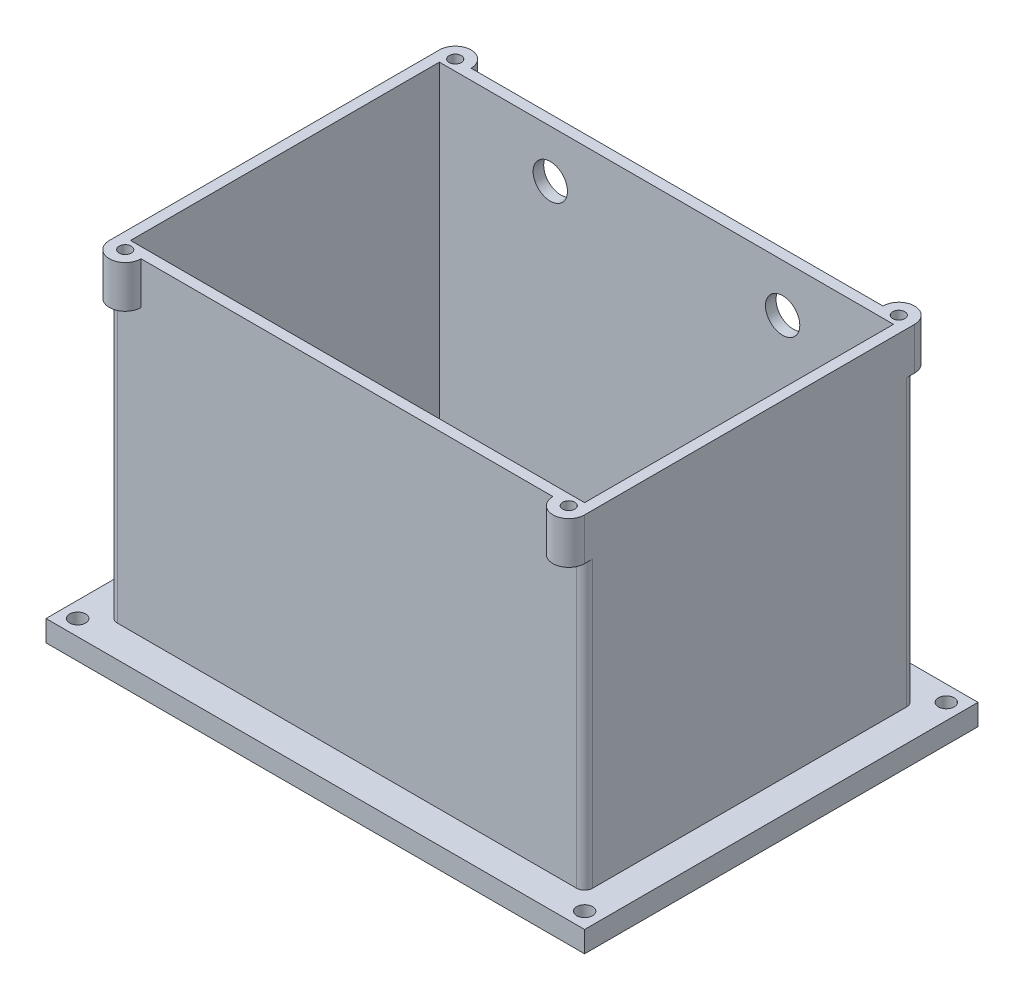
SolidWorks part; units mm, degrees
material "ABS"
ref_plane "Front Plane" through (0, 0, 0) normal (0, 0, 1) x (1, 0, 0)
ref_plane "Top Plane" through (0, 0, 0) normal (0, 1, 0) x (1, 0, 0)
ref_plane "Right Plane" through (0, 0, 0) normal (1, 0, 0) x (0, 0, -1)
sketch "Base" plane through (0, 0, 0) normal (0, 1, 0) x (1, 0, 0)
  line L1 (0, 0) -> (90, 0)
  line L2 (0, 0) -> (0, 62.5)
  line L3 (0, 62.5) -> (90, 62.5)
  line L4 (90, 0) -> (90, 62.5)
  dimension "D1" = 62.5
  dimension "D2" = 90
extrude "Base Extrude" add sketch "Base" along normal blind 2
sketch "Walls" plane through (0, 2, 0) normal (0, 1, 0) x (1, 0, 0)
  line L0 (0, 62.5) -> (0, 0) construction
  line L1 (2, 2) -> (88, 2)
  line L2 (2, 2) -> (2, 60.5)
  line L3 (2, 60.5) -> (88, 60.5)
  line L4 (88, 2) -> (88, 60.5)
  line L5 (90, 62.5) -> (0, 62.5) construction
  dimension "D1" = 86
  dimension "D2" = 58.5
  dimension "D3" = 2
  dimension "D4" = 2
extrude "Walls Extrude" add sketch "Walls" along normal blind 64 thin thin type one direction wall 2
sketch "Outjut" plane through (0, 66, 0) normal (0, 1, 0) x (1, 0, 0)
  line L0 (0, 0) -> (0, 62.5) construction
  line L1 (0, 62.5) -> (6, 62.5)
  line L2 (90, 62.5) -> (84, 62.5)
  line L3 (45, 64) -> (45, 0) construction
  line L4 (0, 0) -> (90, 0) construction
  line L5 (0, 31.25) -> (92, 31.25) construction
  line L6 (90, 0) -> (84, 0)
  line L7 (0, 0) -> (6, 0)
  arc A0 (0, 62.5) -> (6, 62.5) centre (3, 62.5) cw
  arc A1 (90, 62.5) -> (84, 62.5) centre (87, 62.5) ccw
  arc A2 (90, 0) -> (84, 0) centre (87, 0) cw
  arc A3 (0, 0) -> (6, 0) centre (3, 0) ccw
  point P4 (3, 65.5)
  dimension "D1" = 6
  dimension "D2" = 3
extrude "Outjut Extrude" add sketch "Outjut" against normal blind 8
sketch "Holes" plane through (0, 66, 0) normal (0, 1, 0) x (1, 0, 0)
  line L0 (45, 62.5) -> (45, 0) construction
  line L2 (84, 62.5) -> (6, 62.5) construction
  line L3 (6, 0) -> (84, 0) construction
  line L4 (90, 31.25) -> (0, 31.25) construction
  line L5 (90, 0) -> (90, 62.5) construction
  line L6 (0, 62.5) -> (0, 0) construction
  circle A1 centre (3, 62.5) radius 1.15
  circle A2 centre (87, 62.5) radius 1.15
  circle A3 centre (87, 0) radius 1.15
  circle A4 centre (3, 0) radius 1.15
  dimension "D1" = 2.3
extrude "Holes Cut" cut sketch "Holes" against normal blind 6
sketch "Switch Hole" plane through (0, 0, 0) normal (0, 0, 1) x (1, 0, 0)
  line L0 (90, 58) -> (90, 0) construction
  line L2 (0, 0) -> (90, 0) construction
  line L5 (74, 23) -> (85, 23)
  line L6 (74, 23) -> (74, 28)
  line L7 (74, 28) -> (85, 28)
  line L8 (85, 23) -> (85, 28)
  dimension "D1" = 11
  dimension "D2" = 5
  dimension "D3" = 5
  dimension "D4" = 23
extrude "Switch Hole Cut" [suppressed] cut sketch "Switch Hole" against normal up to surface (2 mm away) up to face at (45, 34, -2)
sketch "Antenna/GPS Holes" plane through (0, 0, -62.5) normal (0, 0, -1) x (-1, 0, 0)
  line L0 (-90, 0) -> (0, 0) construction
  line L1 (0, 58) -> (0, 0) construction
  line L2 (-45, 66) -> (-45, 0) construction
  line L3 (-84, 66) -> (-6, 66) construction
  circle A0 centre (-23, 56.95) radius 3.25
  circle A2 centre (-67, 56.95) radius 3.25
  point P12 (0, 0)
  dimension "D1" = 6.5
  dimension "D2" = 56.95
  dimension "D3" = 23
extrude "Antenna/GPS Holes Cut" cut sketch "Antenna/GPS Holes" against normal up to surface (2 mm away) up to face at (45, 34, -60.5)
sketch "Pad" plane through (0, 0, 0) normal (0, -1, 0) x (1, 0, 0)
  line L2 (0, 0) -> (0, -62.5)
  line L4 (-6, 6) -> (-6, -68.5)
  line L5 (0, 0) -> (90, 0)
  line L7 (-6, 6) -> (96, 6)
  line L9 (90, -62.5) -> (0, -62.5)
  line L11 (96, -68.5) -> (-6, -68.5)
  line L14 (90, -62.5) -> (90, 0)
  line L16 (96, -68.5) -> (96, 6)
  point P6 (-6.35, 6.35)
  point P9 (95.25, 6.35)
  point P10 (0, -69.85)
  point P11 (-6.35, -69.85)
  point P12 (-6.35, -69.85)
  point P16 (0, -62.5)
  point P17 (-6.35, -69.85)
  point P19 (0, 0)
  point P20 (-6.35, -63.5)
  point P21 (-12.7, -63.5)
  point P22 (0, 0)
  point P23 (95.25, -69.85)
  point P24 (-6.35, -69.85)
  point P25 (-6.35, -69.85)
  dimension "D1" = 6
  dimension "D2" = 6
  dimension "D3" = 6
  dimension "D4" = 6
extrude "Pad Extrude" add sketch "Pad" against normal blind 4 contours L7 L16 L11 L4
sketch "Screw Holes" plane through (0, 4, 0) normal (0, 1, 0) x (1, 0, 0)
  line L0 (96, 68.5) -> (90, 62.5) construction
  line L1 (45, 68.5) -> (45, -6) construction
  line L2 (96, 68.5) -> (-6, 68.5) construction
  line L3 (-6, -6) -> (96, -6) construction
  line L4 (-6, 31.25) -> (96, 31.25) construction
  line L5 (-6, -6) -> (-6, 68.5) construction
  line L6 (96, 68.5) -> (96, -6) construction
  circle A0 centre (93, 65.5) radius 1.5
  circle A1 centre (-3, 65.5) radius 1.5
  circle A2 centre (93, -3) radius 1.5
  circle A3 centre (-3, -3) radius 1.5
  dimension "D1" = 3
extrude "Screw Holes Cut" cut sketch "Screw Holes" against normal through all
fillet "Wall Fillets" radius 1.5 4 edges at (90, 31, -62.5) (90, 31, 0) (0, 31, 0) (0, 31, -62.5)
